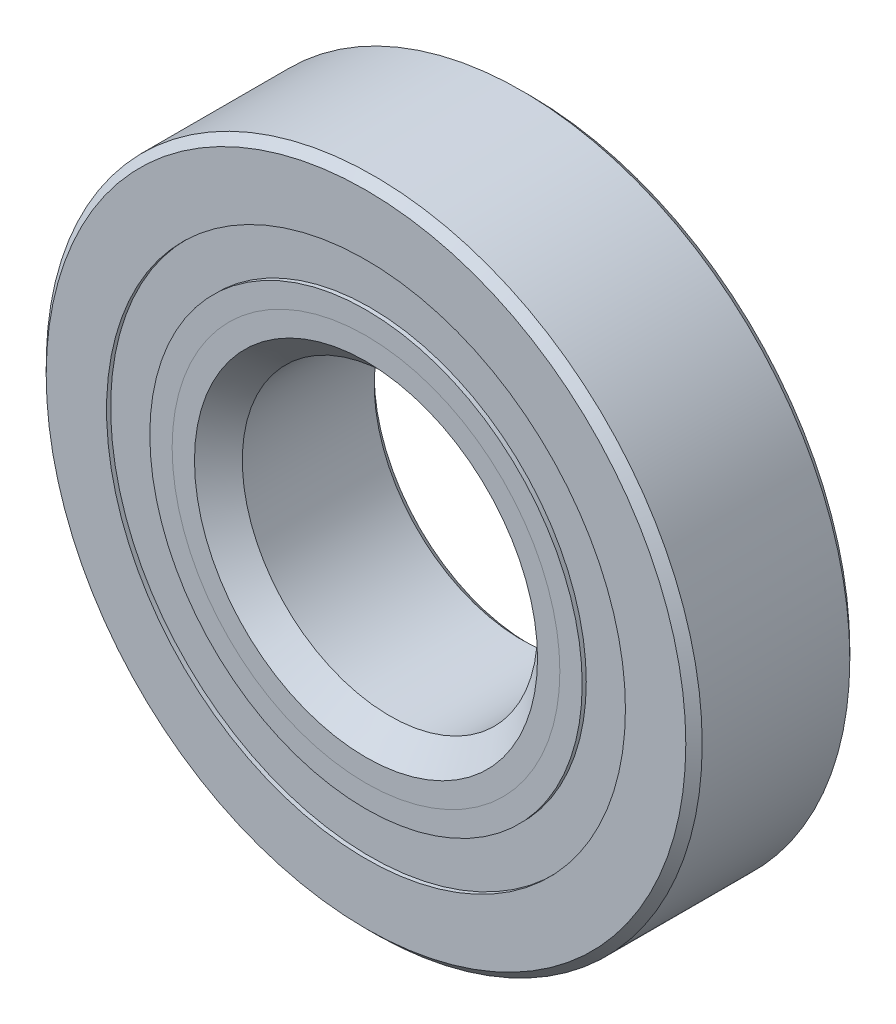
SolidWorks part; units mm, degrees
ref_plane "Front Plane" through (0, 0, 0) normal (0, 0, 1) x (1, 0, 0)
ref_plane "Top Plane" through (0, 0, 0) normal (0, 1, 0) x (1, 0, 0)
ref_plane "Right Plane" through (0, 0, 0) normal (1, 0, 0) x (0, 0, -1)
sketch "Sketch1" plane through (0, 0, 0) normal (1, 0, 0) x (0, 0, -1)
  line L0 (-7.9375, 0) -> (7.9375, 0) construction
  line L1 (0, 31.75) -> (0, -31.75) construction
  line L2 (7.1437, 31.75) -> (-7.1438, 31.75)
  line L3 (-7.1438, 31.75) -> (-7.9375, 30.9563)
  line L4 (-7.9375, 30.9563) -> (-7.9375, 25.1122)
  line L5 (-7.9375, 25.1122) -> (-3.5278, 25.1122)
  line L6 (7.9375, 25.1122) -> (3.5278, 25.1122)
  line L7 (7.9375, 30.9563) -> (7.9375, 25.1122)
  line L8 (7.1437, 31.75) -> (7.9375, 30.9563)
  line L9 (0, 31.75) -> (0, 23.0187) construction
  line L10 (0, 23.0187) -> (0, 14.2875) construction
  arc A0 (-3.5278, 25.1122) -> (3.5278, 25.1122) centre (0, 23.0187) cw
  point P14 (0, 14.2875)
  dimension "D3" = 7.0556
  dimension "D1" = 45
  dimension "Width" = 15.875
  dimension "OD" = 63.5
  dimension "D2" = 0.7937
  dimension "Shaft Dia" = 28.575
  dimension "D4" = 2.0934
revolve "Revolve1" add sketch "Sketch1" angle 360 about L0
sketch "Sketch2" plane through (0, 0, 0) normal (1, 0, 0) x (0, 0, -1)
  line L0 (-7.9375, 20.9253) -> (-3.5278, 20.9253)
  line L1 (-7.9375, 30.9563) -> (-7.9375, -30.9563) construction
  line L2 (-7.9375, 20.9253) -> (-7.9375, 18.7637)
  line L3 (-7.9375, 18.7637) -> (-5.7759, 16.6021)
  line L4 (-5.7759, 16.6021) -> (0, 16.6021)
  line L5 (0, 31.75) -> (0, -31.75) construction
  line L6 (0, 16.6021) -> (0, 18.9166)
  line L7 (0, 18.9166) -> (0, 14.2875) construction
  line L8 (-7.9375, 20.9253) -> (-7.9375, 16.6021) construction
  line L9 (-7.9375, 16.6021) -> (-5.7759, 16.6021) construction
  arc A0 (-3.5278, 20.9253) -> (0, 18.9166) centre (0, 23.0187) ccw
  arc A1 (3.5278, 25.1122) -> (-3.5278, 25.1122) centre (0, 23.0187) ccw construction
  circle A2 centre (0, 23.0187) radius 4.1021 construction
  dimension "D1" = 45
revolve "Revolve2" add sketch "Sketch2" angle 360 about L0
sketch "Sketch3" plane through (0, 0, 0) normal (1, 0, 0) x (0, 0, -1)
  line L0 (-7.9375, 18.7637) -> (-5.7759, 16.6021)
  line L1 (-5.7759, 16.6021) -> (0, 16.6021)
  line L2 (0, 16.6021) -> (0, 18.9166)
  line L3 (-7.9375, 18.7637) -> (-7.9375, 16.6021)
  line L4 (-7.9375, 20.9253) -> (-7.9375, 16.6021) construction
  line L5 (-7.9375, 16.6021) -> (-5.6229, 14.2875)
  line L6 (-5.6229, 14.2875) -> (7.1438, 14.2875)
  line L7 (7.1438, 31.75) -> (7.1438, -31.75) construction
  line L8 (7.1438, 14.2875) -> (7.9375, 15.0812)
  line L9 (7.9375, -30.9563) -> (7.9375, 30.9563) construction
  line L10 (7.9375, 15.0812) -> (7.9375, 20.9253)
  line L11 (7.9375, 20.9253) -> (3.5278, 20.9253)
  line L13 (7.1437, 31.75) -> (7.9375, 30.9563) construction
  circle A0 centre (0, 23.0187) radius 4.1021 construction
  arc A1 (3.5278, 20.9253) -> (0, 18.9166) centre (0, 23.0187) cw
revolve "Revolve3" add sketch "Sketch3" angle 360 about L0
sketch "Sketch4" plane through (0, 0, 0) normal (1, 0, 0) x (0, 0, -1)
  line L0 (-4.1021, 23.0187) -> (4.1021, 23.0187)
  circle A1 centre (0, 23.0187) radius 4.1021 construction
  arc A2 (-4.1021, 23.0187) -> (4.1021, 23.0187) centre (0, 23.0187) cw
  arc A3 (3.5278, 25.1122) -> (-3.5278, 25.1122) centre (0, 23.0187) ccw construction
revolve "Revolve4" add sketch "Sketch4" angle 360 about L0
ref_axis "Axis1" through (0, 0, -7.9375) along (0, 0, 1)
pattern_circular "CirPattern1" count 12 every 30 about axis through (0, 0, -7.9375) along (0, 0, 1) of bodies 104
sketch "Sketch5" plane through (0, 0, 0) normal (1, 0, 0) x (0, 0, -1)
  line L0 (-7.9375, 25.1122) -> (-3.5278, 25.1122) construction
  line L1 (-7.5406, 25.1122) -> (-4.1021, 25.1122)
  line L2 (-7.5406, 25.1122) -> (-7.5406, 20.9253)
  line L3 (-7.5406, 20.9253) -> (-4.1021, 20.9253)
  line L4 (-4.1021, 25.1122) -> (-4.1021, 20.9253)
  line L5 (-7.9375, 20.9253) -> (-3.5278, 20.9253) construction
  line L6 (-7.1438, 31.75) -> (-7.9375, 30.9563) construction
  line L7 (0, 31.75) -> (0, 14.2875) construction
  line L8 (7.5406, 20.9253) -> (4.1021, 20.9253)
  line L9 (4.1021, 25.1122) -> (4.1021, 20.9253)
  line L10 (7.5406, 25.1122) -> (4.1021, 25.1122)
  line L11 (7.5406, 25.1122) -> (7.5406, 20.9253)
  circle A0 centre (0, 23.0187) radius 4.1021 construction
  point P10 (-7.5406, 31.3531)
revolve "Revolve5" add sketch "Sketch5" angle 360 about L0
equation "\"D2@Sketch1\" = \"Width@Sketch1\"*.05"
equation "\"D3@Sketch1\" = \"Width@Sketch1\"/2.25"
equation "\"D4@Sketch1\" = (((\"OD@Sketch1\"-\"Width@Sketch1\")/2)/3.25)/3.5"
equation "\"D2@CirPattern1\" = 360/\"Balls@CirPattern1\""
